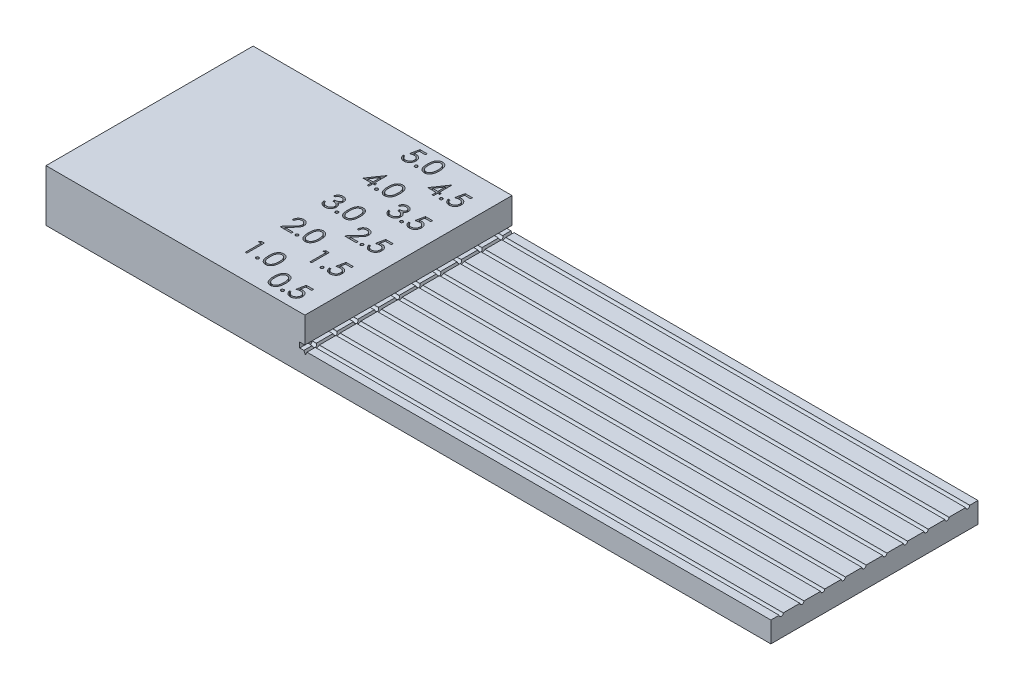
SolidWorks part; units mm, degrees
ref_plane "Front Plane" through (0, 0, 0) normal (0, 0, 1) x (1, 0, 0)
ref_plane "Top Plane" through (0, 0, 0) normal (0, 1, 0) x (1, 0, 0)
ref_plane "Right Plane" through (0, 0, 0) normal (1, 0, 0) x (0, 0, -1)
sketch "Sketch2" plane through (0, 0, 0) normal (0, 1, 0) x (1, 0, 0)
  line L1 (-35, -10) -> (35, -10)
  line L2 (-35, -10) -> (-35, 10)
  line L3 (-35, 10) -> (35, 10)
  line L4 (35, -10) -> (35, 10)
  line L5 (-35, -10) -> (35, 10) construction
  line L6 (-35, 10) -> (35, -10) construction
  point P0 (0, 0)
  dimension "D1" = 70
  dimension "D2" = 20
extrude "Boss-Extrude1" add sketch "Sketch2" along normal blind 2
sketch "Sketch3" plane through (0, 2, 0) normal (0, 1, 0) x (1, 0, 0)
  line L0 (35, 10) -> (-35, 10) construction
  line L1 (-35, -10) -> (-10, -10)
  line L2 (-35, -10) -> (-35, 10)
  line L3 (-35, 10) -> (-10, 10)
  line L4 (-10, -10) -> (-10, 10)
  dimension "D1" = 25
extrude "Boss-Extrude2" add sketch "Sketch3" along normal blind 3
sketch "Sketch9" plane through (0, 2, 0) normal (0, 1, 0) x (1, 0, 0)
  line L0 (-10, -10) -> (-10.5, -10)
  line L1 (-10.5, -10) -> (-10.5, -8)
  line L2 (-10, -10) -> (-10, 10) construction
  line L3 (-10.5, -8) -> (-11.162, -8)
  line L4 (-11.162, -8) -> (-11.162, -6)
  line L5 (-11.162, -6) -> (-11.662, -6)
  line L6 (-11.662, -6) -> (-11.662, -4)
  line L7 (-11.662, -4) -> (-12.162, -4)
  line L8 (-12.162, -4) -> (-12.162, -2)
  line L9 (-12.162, -2) -> (-12.662, -2)
  line L10 (-12.662, -2) -> (-12.662, 0)
  line L11 (-12.662, 0) -> (-13.162, 0)
  line L12 (-13.162, 0) -> (-13.162, 2)
  line L13 (-13.162, 2) -> (-13.662, 2)
  line L14 (-13.662, 2) -> (-13.662, 4)
  line L15 (-13.662, 4) -> (-14.162, 4)
  line L16 (-14.162, 4) -> (-14.162, 6)
  line L17 (-14.162, 6) -> (-14.662, 6)
  line L18 (-14.662, 6) -> (-14.662, 8)
  line L19 (-14.662, 8) -> (-15.162, 8)
  line L20 (-15.162, 8) -> (-15.162, 10)
  line L21 (-15.162, 10) -> (-10, 10)
  line L22 (-10, 10) -> (-10, -10)
  dimension "D1" = 0.5
  dimension "D2" = 2
  dimension "D3" = 0.5
  dimension "D4" = 0.5
  dimension "D5" = 0.5
  dimension "D6" = 0.5
  dimension "D7" = 0.5
  dimension "D8" = 2
  dimension "D9" = 2
  dimension "D10" = 2
  dimension "D11" = 2
  dimension "D12" = 2
  dimension "D13" = 2
  dimension "D14" = 0.5
  dimension "D15" = 0.5
  dimension "D16" = 0.5
  dimension "D17" = 2
  dimension "D18" = 2
  dimension "D19" = 2
extrude "Cut-Extrude9" cut sketch "Sketch9" along normal blind 0.5 contours L10 L11 L12 L13 L14 L15 L16 L17 L18 L19 L20 L21 L22 L0 L1 L3 L4 L5 L6 L7 L8 L9
sketch "Sketch6" plane through (0, 0, 10) normal (0, 0, 1) x (1, 0, 0)
  line L8 (-9.95, 2) -> (-9.95, 1.7) construction
  line L9 (-10.5, 2) -> (35, 2) construction
  line L11 (-9.95, 1.7) -> (-10.1, 2)
  line L12 (-10.1, 2) -> (-9.8, 2)
  line L13 (-9.8, 2) -> (-9.95, 1.7)
  line L14 (-10, 5) -> (-10, 2.5) construction
  dimension "D1" = 0.3
  dimension "D2" = 0.3
  dimension "D3" = 0.05
extrude "Cut-Extrude6" cut sketch "Sketch6" against normal through all contours L13 L11 L12
sketch "Sketch10" plane through (35, 0, 0) normal (1, 0, 0) x (0, 0, -1)
  line L0 (-10, 2) -> (10, 2) construction
  line L1 (-10, 2) -> (-8, 2) construction
  circle A0 centre (-9, 2) radius 0.2
  circle A1 centre (-7, 2) radius 0.2
  circle A2 centre (-5, 2) radius 0.2
  circle A3 centre (-3, 2) radius 0.2
  circle A4 centre (-1, 2) radius 0.2
  circle A5 centre (1, 2) radius 0.2
  circle A6 centre (3, 2) radius 0.2
  circle A7 centre (5, 2) radius 0.2
  circle A8 centre (7, 2) radius 0.2
  circle A9 centre (9, 2) radius 0.2
  point P6 (-9, 2)
  point P7 (0, 0)
  line M4 (10, 2) -> (-10, 2)
  dimension "D1" = 0.4
  dimension "D2" = 10
extrude "Cut-Extrude10" cut sketch "Sketch10" against normal up to surface (45.5 mm away) contours A0 M4 | A0 M4 region at (35, 2.0849, 9) region at (35, 1.9151, 9) up to face at (-10.5, 2.25, 9)
extrude "Cut-Extrude11" cut sketch "Sketch10<3>" against normal up to surface (46.162 mm away) contours A1 up to face at (-11.162, 2.25, 7)
sketch "Sketch10<3>" plane through (35, 0, 0) normal (1, 0, 0) x (0, 0, -1) same geometry as "Sketch10"
extrude "Cut-Extrude12" cut sketch "Sketch10<4>" against normal up to surface (46.662 mm away) contours A2 up to face at (-11.662, 2.25, 5)
sketch "Sketch10<4>" plane through (35, 0, 0) normal (1, 0, 0) x (0, 0, -1) same geometry as "Sketch10"
extrude "Cut-Extrude13" cut sketch "Sketch10<5>" against normal up to surface (47.162 mm away) contours A3 up to face at (-12.162, 2.25, 3)
sketch "Sketch10<5>" plane through (35, 0, 0) normal (1, 0, 0) x (0, 0, -1) same geometry as "Sketch10"
extrude "Cut-Extrude14" cut sketch "Sketch10<6>" against normal up to surface (47.662 mm away) contours A4 up to face at (-12.662, 2.25, 1)
sketch "Sketch10<6>" plane through (35, 0, 0) normal (1, 0, 0) x (0, 0, -1) same geometry as "Sketch10"
extrude "Cut-Extrude15" cut sketch "Sketch10<7>" against normal up to surface (48.162 mm away) contours A5 up to face at (-13.162, 2.25, -1)
sketch "Sketch10<7>" plane through (35, 0, 0) normal (1, 0, 0) x (0, 0, -1) same geometry as "Sketch10"
extrude "Cut-Extrude16" cut sketch "Sketch10<8>" against normal up to surface (48.662 mm away) contours A6 up to face at (-13.662, 2.25, -3)
sketch "Sketch10<8>" plane through (35, 0, 0) normal (1, 0, 0) x (0, 0, -1) same geometry as "Sketch10"
extrude "Cut-Extrude17" cut sketch "Sketch10<9>" against normal up to surface (49.162 mm away) contours A7 up to face at (-14.162, 2.25, -5)
sketch "Sketch10<9>" plane through (35, 0, 0) normal (1, 0, 0) x (0, 0, -1) same geometry as "Sketch10"
extrude "Cut-Extrude18" cut sketch "Sketch10<10>" against normal up to surface (49.662 mm away) contours A8 up to face at (-14.662, 2.25, -7)
sketch "Sketch10<10>" plane through (35, 0, 0) normal (1, 0, 0) x (0, 0, -1) same geometry as "Sketch10"
extrude "Cut-Extrude19" cut sketch "Sketch10<11>" against normal up to surface (50.162 mm away) contours A9 up to face at (-15.162, 2.25, -9)
sketch "Sketch10<11>" plane through (35, 0, 0) normal (1, 0, 0) x (0, 0, -1) same geometry as "Sketch10"
sketch "Sketch7" plane through (0, 5, 0) normal (0, 1, 0) x (1, 0, 0)
  line L5 (-18.7196, 7.7) -> (-11.2945, 7.7) construction
  line L6 (-10, 10) -> (-35, 10) construction
  line L7 (5.5917, -10.9577) -> (15.7658, -10.9577) construction
  line L8 (-14.7974, 6.2) -> (-1.7391, 6.2) construction
  text T0 "5.0\r\n4.0\r\n3.0\r\n2.0\r\n1.0" font "Century Gothic" height 1.7
  text T1 "4.5\r\n3.5\r\n2.5\r\n1.5\r\n0.5" font "Century Gothic" height 1.7
  point P5 (-21.4686, 9)
  point P10 (-15.2141, 6.5)
  point P11 (-17.1452, 8)
  point P12 (-13.4023, 6.5)
  point P13 (-18.0742, 8)
  point P14 (-14.3794, 6.5)
  point P15 (0, 0)
  point P16 (-19.5086, 8)
  point P17 (0, 0)
  point P18 (-18.7196, 7.7)
  point P19 (-14.7974, 6.2)
  dimension "D1" = 2.3
  dimension "D2" = 1.5
extrude "Cut-Extrude7" cut sketch "Sketch7" against normal blind 0.5
